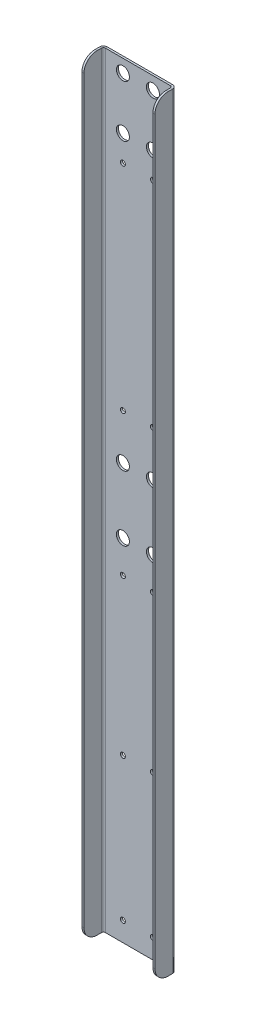
SolidWorks part; units mm, degrees
note: The reader was unsure of these and kept them because the rebuilt part matched: thickness of "Base-Flange1", "Edge-Flange2", "Sheet-Metal1", "Sheet-Metal3", "Sheet-Metal4", "Sheet-Metal5", "Sheet-Metal6"; flange length of "Edge-Flange2".
material "Alloy Steel"
ref_plane "Front Plane" through (0, 0, 0) normal (0, 0, 1) x (1, 0, 0)
ref_plane "Top Plane" through (0, 0, 0) normal (0, 1, 0) x (1, 0, 0)
ref_plane "Right Plane" through (0, 0, 0) normal (1, 0, 0) x (0, 0, -1)
sketch "Sketch1" plane through (0, 0, 0) normal (0, 0, 1) x (1, 0, 0)
  line L1 (-31.75, 0) -> (31.75, 0)
  line L2 (-31.75, 0) -> (-31.75, 749.3)
  line L3 (-31.75, 749.3) -> (31.75, 749.3)
  line L4 (31.75, 0) -> (31.75, 749.3)
  point P4 (0, 0)
  dimension "D1" = 63.5
  dimension "D2" = 749.3
base flange "Base-Flange1" sketch "Sketch1" thickness 1.9844 reverse thickness direction no parameters "D1"=1.9844
sketch "Sketch9" plane through (0, 0, 0) normal (0, 0, 1) x (1, 0, 0)
  line L1 (-14.6844, 406.4) -> (14.6844, 406.4) construction
  line L2 (-14.6844, 406.4) -> (-14.6844, 342.9) construction
  line L3 (-14.6844, 342.9) -> (14.6844, 342.9) construction
  line L4 (14.6844, 406.4) -> (14.6844, 342.9) construction
  line L7 (31.75, 749.3) -> (-31.75, 749.3) construction
  point P11 (0, 342.9)
  dimension "D1" = 29.3687
  dimension "D2" = 63.5
  dimension "D3" = 342.9
hole_wizard "1/2 (0.5) Diameter Hole1" positions "Sketch12" profile "Sketch13" hole size "1/2" standard "ANSI Inch" end condition through all
sketch "Sketch12" plane through (0, 0, 0) normal (0, 0, 1) x (1, 0, 0)
  point P0 (-14.6844, 406.4)
  point P3 (14.6844, 406.4)
  point P6 (14.6844, 342.9)
  point P9 (-14.6844, 342.9)
sketch "Sketch13" plane through (-14.6844, 406.4, 0) normal (1, 0, 0) x (0, -1, 0)
  line L0 (0, 0) -> (0, 1.9844)
  line L1 (0, 1.9844) -> (6.35, 1.9844)
  line L2 (6.35, 1.9844) -> (6.35, 0)
  line L5 (6.35, 0) -> (0, 0)
  line L11 (0, -6.35) -> (0, 107.95) construction
  dimension "Thru Hole Dia." = 12.7
  dimension "Thru Hole Depth" = 1.9844
sketch "Sketch14" plane through (0, 0, 0) normal (0, 0, 1) x (1, 0, 0)
  line L0 (-14.6844, 406.4) -> (-14.6844, 342.9) construction
  line L1 (-14.6844, 736.6) -> (14.6844, 736.6)
  line L2 (-14.6844, 736.6) -> (-14.6844, 685.8)
  line L3 (-14.6844, 685.8) -> (14.6844, 685.8)
  line L4 (14.6844, 736.6) -> (14.6844, 685.8)
  line L5 (14.6844, 406.4) -> (14.6844, 342.9) construction
  line L6 (31.75, 749.3) -> (-31.75, 749.3) construction
  line L7 (-14.6844, 406.4) -> (14.6844, 406.4) construction
  dimension "D1" = 50.8
  dimension "D2" = 12.7
  dimension "D3" = 279.4
hole_wizard "1/2 (0.5) Diameter Hole2" positions "Sketch15" profile "Sketch16" hole size "1/2" standard "ANSI Inch" end condition through all
sketch "Sketch15" plane through (0, 0, 0) normal (0, 0, 1) x (1, 0, 0)
  point P9 (14.6844, 685.8)
  point P11 (14.6844, 736.6)
  point P13 (-14.6844, 736.6)
  point P15 (-14.6844, 685.8)
sketch "Sketch16" plane through (14.6844, 685.8, 0) normal (1, 0, 0) x (0, -1, 0)
  line L0 (0, 0) -> (0, 1.9844)
  line L1 (0, 1.9844) -> (6.35, 1.9844)
  line L2 (6.35, 1.9844) -> (6.35, 0)
  line L5 (6.35, 0) -> (0, 0)
  line L11 (0, -6.35) -> (0, 107.95) construction
  dimension "Thru Hole Dia." = 12.7
  dimension "Thru Hole Depth" = 1.9844
edge flange "Edge-Flange2" sketch "Sketch21" flange profiles "Sketch21", "Sketch22" flange angle 90 flange length 19.05 flange position bend outside bend radius 1.9844 thickness 1.9844 relief rectangular parameters "D1"=2.9766, "D6"=10, "D8"=1
sketch "Sketch21" plane through (-31.75, 0, 0) normal (-1, 0, 0) x (0, -1, 0)
  line L2 (-749.3, 0) -> (-749.3, 19.05)
  line L3 (-749.3, 19.05) -> (0, 19.05)
  line L4 (0, 19.05) -> (0, 0)
  line L7 (-749.3, 0) -> (0, 0) construction
  line L8 (-749.3, 0) -> (0, 0)
sketch "Sketch22" plane through (31.75, 0, 0) normal (1, 0, 0) x (0, 1, 0)
  line L0 (0, 0) -> (749.3, 0) construction
  line L1 (0, 0) -> (749.3, 0)
  line L2 (0, 0) -> (0, 19.05)
  line L3 (0, 19.05) -> (749.3, 19.05)
  line L4 (749.3, 19.05) -> (749.3, 0)
bend "EdgeBend2" bend radius 1.9844 bend angle 90 parameters "D5"=2
bend "EdgeBend3" bend radius 1.9844 bend angle 90 parameters "D5"=3
sketch "Sketch23" plane through (0, 0, -1.9844) normal (0, 0, -1) x (-1, 0, 0)
  line L0 (31.75, 0) -> (-31.75, 0) construction
  line L1 (-14.6844, 736.6) -> (14.6844, 736.6) construction
  line L2 (-14.6844, 736.6) -> (-14.6844, 0) construction
  line L3 (-14.6844, 0) -> (14.6844, 0) construction
  line L4 (14.6844, 736.6) -> (14.6844, 0) construction
  line L5 (-14.6844, 679.45) -> (14.6844, 679.45) construction
  line L6 (-31.75, 749.3) -> (31.75, 749.3) construction
  line L7 (-14.6844, 660.4) -> (14.6844, 660.4) construction
  line L10 (14.6844, 660.4) -> (-14.6844, 450.85) construction
  line L11 (-14.6844, 450.85) -> (14.6844, 450.85) construction
  line L12 (14.6844, 450.85) -> (-14.6844, 336.55) construction
  line L13 (-14.6844, 336.55) -> (14.6844, 336.55) construction
  line L14 (14.6844, 336.55) -> (-14.6844, 311.15) construction
  line L15 (-14.6844, 311.15) -> (14.6844, 311.15) construction
  line L16 (14.6844, 311.15) -> (-14.6844, 158.75) construction
  line L17 (-14.6844, 158.75) -> (14.6844, 158.75) construction
  line L18 (14.6844, 158.75) -> (-14.6844, 19.05) construction
  line L19 (-14.6844, 19.05) -> (14.6844, 19.05) construction
  circle A0 centre (-14.6844, 685.8) radius 6.35 construction
  circle A1 centre (-14.6844, 342.9) radius 6.35 construction
  dimension "D1" = 209.55
  dimension "D2" = 139.7
  dimension "D3" = 152.4
  dimension "D4" = 139.7
  dimension "D5" = 88.9
hole_wizard "#10 (0.201) Diameter Hole1" positions "Sketch24" profile "Sketch25" hole size "#10" standard "ANSI Inch" end condition through all
sketch "Sketch24" plane through (0, 0, -1.9844) normal (0, 0, -1) x (-1, 0, 0)
  point P0 (-14.6844, 19.05)
  point P3 (14.6844, 19.05)
  point P6 (-14.6844, 158.75)
  point P9 (14.6844, 158.75)
  point P12 (-14.6844, 311.15)
  point P15 (14.6844, 311.15)
  point P18 (-14.6844, 450.85)
  point P21 (14.6844, 450.85)
  point P30 (-14.6844, 660.4)
  point P40 (14.6844, 660.4)
sketch "Sketch25" plane through (14.6844, 19.05, -1.9844) normal (1, 0, 0) x (0, 1, 0)
  line L0 (0, 0) -> (0, 21.0344)
  line L1 (0, 21.0344) -> (2.4574, 21.0344)
  line L2 (2.4574, 21.0344) -> (2.4574, 0)
  line L5 (2.4574, 0) -> (0, 0)
  line L11 (0, -6.35) -> (0, 107.95) construction
  dimension "Thru Hole Dia." = 4.9149
  dimension "Thru Hole Depth" = 21.0344
fillet "Fillet1" radius 12.7 4 edges at (-34.7266, 0, 19.05) (34.7266, 0, 19.05) (34.7266, 749.3, 19.05) (-34.7266, 749.3, 19.05)
sketch "Bend-Lines1" [suppressed] plane through (0, 0, 0) normal (0, 1, 0) x (1, 0, 0)
sketch "Bounding-Box1" [suppressed] plane through (0, 0, 0) normal (0, 1, 0) x (1, 0, 0)
sheet metal parameters "Sheet-Metal1" thickness 1.9844 parameters "D1"=1.27, "D7"=3.175
flat pattern "Flat-Pattern1" [suppressed]
sketch "Bend-Lines2" plane through (0, 0, 0) normal (0, 1, 0) x (1, 0, 0)
sketch3d "Bounding-Box2" [suppressed]
  line L0 (-31.75, 865.1875, 0) -> (-31.75, 0, 0) construction
  line L1 (31.75, 865.1875, 0) -> (31.75, 0, 0) construction
  line L2 (-31.75, 865.1875, 0) -> (31.75, 865.1875, 0) construction
  line L3 (-31.75, 0, 0) -> (31.75, 0, 0) construction
sheet metal parameters "Sheet-Metal3" thickness 1.9844 parameters "D1"=1.27, "D7"=3.175
flat pattern "Flat-Pattern1"
sketch "Bend-Lines2" plane through (0, 0, 0) normal (0, 0, 1) x (1, 0, 0)
  line L0 (-31.75, 3.0539) -> (31.75, 3.0539) construction
  line L1 (-31.75, 3.0539) -> (31.75, 3.0539) construction
sketch3d "Bounding-Box2" [suppressed]
  line L0 (31.75, 847.725, 0) -> (31.75, -108.8029, 0) construction
  line L1 (-31.75, 847.725, 0) -> (-31.75, -108.8029, 0) construction
  line L2 (31.75, 847.725, 0) -> (-31.75, 847.725, 0) construction
  line L3 (31.75, -108.8029, 0) -> (-31.75, -108.8029, 0) construction
sheet metal parameters "Sheet-Metal4" thickness 1.9844 parameters "D1"=1.27, "D7"=3.175
flat pattern "Flat-Pattern1"
sketch "Bend-Lines2" plane through (0, 0, 0) normal (0, 0, 1) x (1, 0, 0)
  line L0 (-31.75, 3.0539) -> (31.75, 3.0539) construction
  line L1 (-31.75, 3.0539) -> (31.75, 3.0539) construction
sketch3d "Bounding-Box2" [suppressed]
  line L0 (31.75, 847.725, 0) -> (31.75, -108.8029, 0) construction
  line L1 (-31.75, 847.725, 0) -> (-31.75, -108.8029, 0) construction
  line L2 (31.75, 847.725, 0) -> (-31.75, 847.725, 0) construction
  line L3 (31.75, -108.8029, 0) -> (-31.75, -108.8029, 0) construction
sheet metal parameters "Sheet-Metal5" thickness 1.9844 parameters "D1"=1.27, "D7"=3.175
flat pattern "Flat-Pattern1"
sketch "Bend-Lines2" plane through (0, 0, 0) normal (0, 0, 1) x (1, 0, 0)
  line L2 (33.9943, 0) -> (33.9943, 749.3) construction
  line L3 (-33.9943, 749.3) -> (-33.9943, 0) construction
  line L4 (33.9943, 0) -> (33.9943, 749.3) construction
  line L5 (-33.9943, 749.3) -> (-33.9943, 0) construction
sketch3d "Bounding-Box2" [suppressed]
  line L0 (54.0185, 0, 0) -> (54.0186, 749.3, 0) construction
  line L1 (-54.0186, 0, 0) -> (-54.0185, 749.3, 0) construction
  line L2 (54.0185, 0, 0) -> (-54.0186, 0, 0) construction
  line L3 (54.0186, 749.3, 0) -> (-54.0185, 749.3, 0) construction
bend of the flat pattern "Flatten-<EdgeBend2>1"
bend of the flat pattern "Flatten-<EdgeBend3>1"
sheet metal parameters "Sheet-Metal6" thickness 1.9844 parameters "D1"=1.27, "D7"=3.175
flat pattern "Flat-Pattern1"
sketch "Bend-Lines2" plane through (0, 0, 0) normal (0, 0, 1) x (1, 0, 0)
  line L2 (34.0878, 0) -> (34.0878, 749.3) construction
  line L3 (-34.0878, 749.3) -> (-34.0878, 0) construction
  line L4 (34.0878, 0) -> (34.0878, 749.3) construction
  line L5 (-34.0878, 749.3) -> (-34.0878, 0) construction
sketch3d "Bounding-Box2" [suppressed]
  line L0 (53.4912, 0, 0) -> (53.4912, 749.3, 0) construction
  line L1 (-53.4912, 0, 0) -> (-53.4912, 749.3, 0) construction
  line L2 (53.4912, 0, 0) -> (-53.4912, 0, 0) construction
  line L3 (53.4912, 749.3, 0) -> (-53.4912, 749.3, 0) construction
bend of the flat pattern "Flatten-<EdgeBend2>1"
bend of the flat pattern "Flatten-<EdgeBend3>1"
